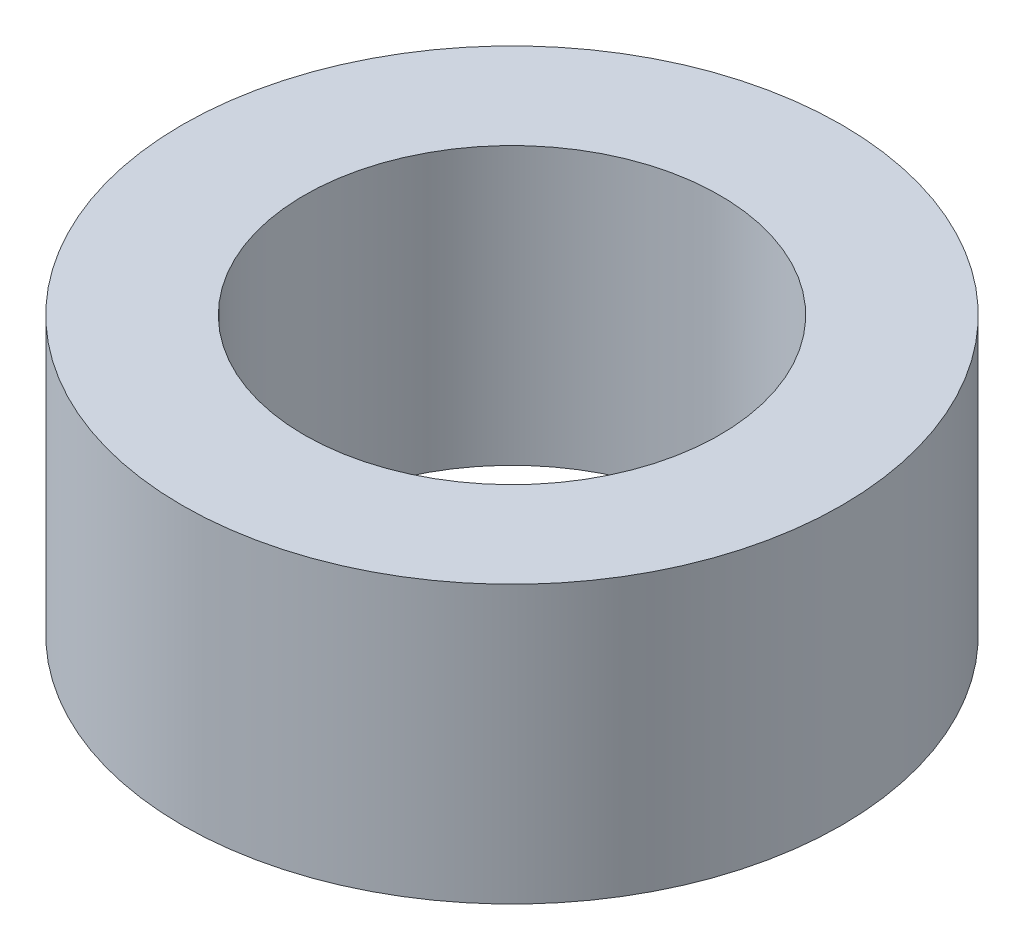
SolidWorks part; units mm, degrees
ref_plane "Front Plane" through (0, 0, 0) normal (0, 0, 1) x (1, 0, 0)
ref_plane "Top Plane" through (0, 0, 0) normal (0, 1, 0) x (1, 0, 0)
ref_plane "Right Plane" through (0, 0, 0) normal (1, 0, 0) x (0, 0, -1)
sketch "Sketch1" plane through (0, 0, 0) normal (0, 1, 0) x (1, 0, 0)
  circle A0 centre (0, 0) radius 6.35
  dimension "D1" = 12.7
extrude "Boss-Extrude1" add sketch "Sketch1" along normal blind 5.334
sketch "Sketch2" plane through (0, 5.334, 0) normal (0, 1, 0) x (1, 0, 0)
  circle A0 centre (0, 0) radius 4
  dimension "D1" = 8
sketch "Sketch3" plane through (0, 5.334, 0) normal (0, 1, 0) x (1, 0, 0)
  circle A0 centre (0, 0) radius 4
  dimension "D1" = 8
extrude "Cut-Extrude2" cut sketch "Sketch3" against normal through all
